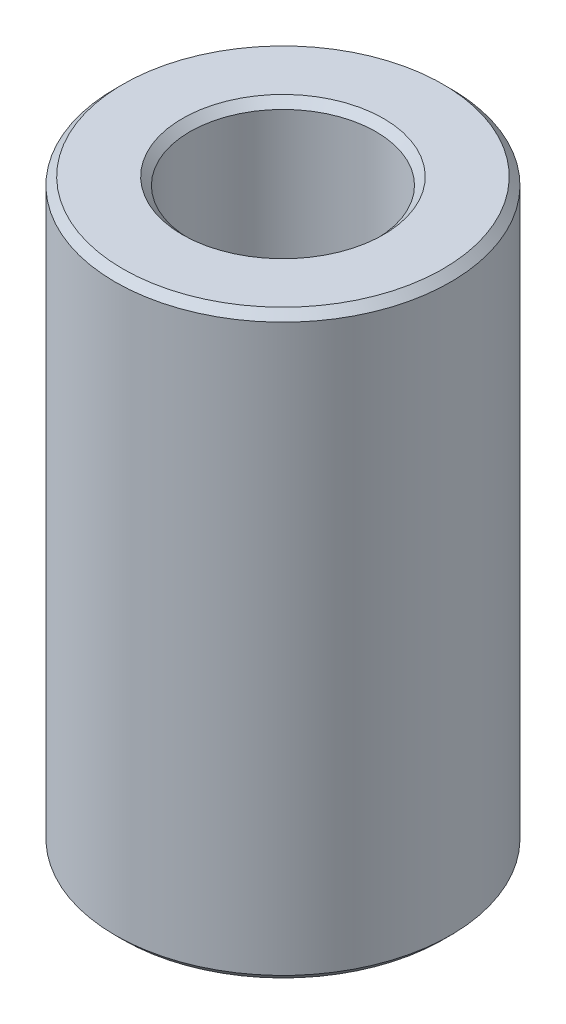
SolidWorks part; units mm, degrees
ref_plane "Front Plane" through (0, 0, 0) normal (0, 0, 1) x (1, 0, 0)
ref_plane "Top Plane" through (0, 0, 0) normal (0, 1, 0) x (1, 0, 0)
ref_plane "Right Plane" through (0, 0, 0) normal (1, 0, 0) x (0, 0, -1)
sketch "Sketch1" plane through (0, 0, 0) normal (0, 1, 0) x (1, 0, 0)
  circle A0 centre (0, 0) radius 27.5
  dimension "SLEEVE_OD" = 55
extrude "Boss-Extrude1" add sketch "Sketch1" along normal blind 95.3081
sketch "Sketch2" plane through (0, 0, 0) normal (0, 1, 0) x (1, 0, 0)
  circle A0 centre (0, 0) radius 15.2647
  dimension "BORE_D" = 30.5294
extrude "Cut-Extrude1" cut sketch "Sketch2" along normal through all
chamfer "Chamfer1" distance 1.2471 angle 45 4 edges at (0, 95.3081, 15.2647) (0, 0, 15.2647) (0, 0, 27.5) (0, 95.3081, 27.5)
